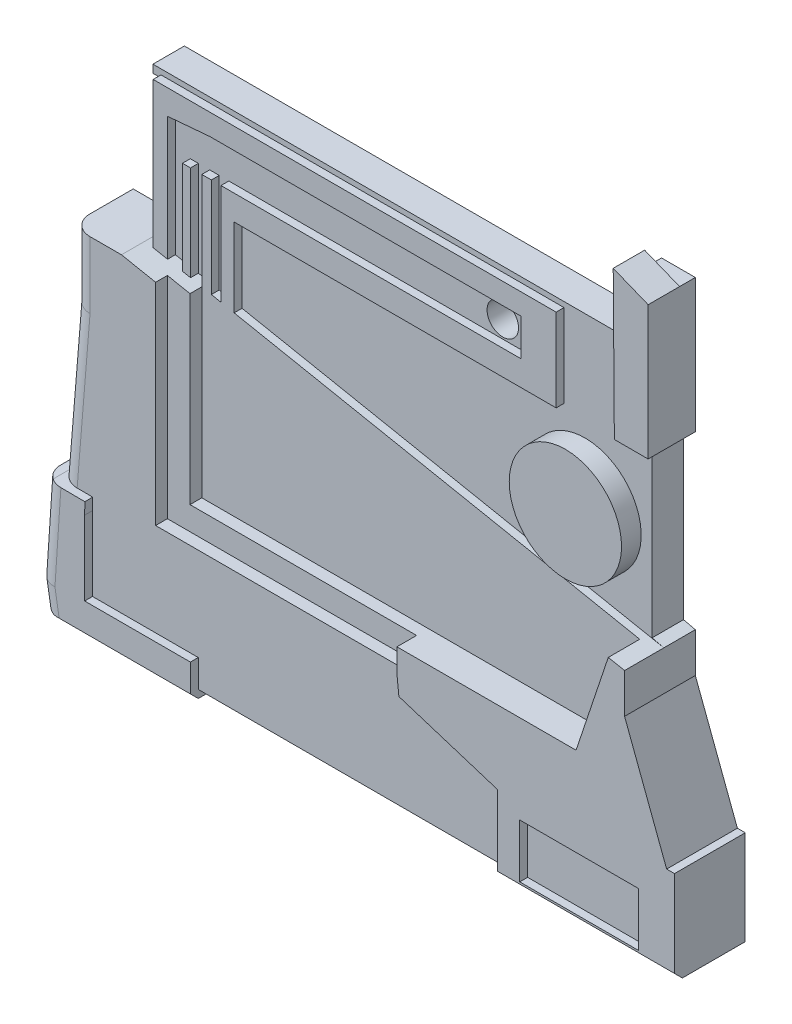
SolidWorks part; units mm, degrees
ref_plane "Front Plane" through (0, 0, 0) normal (0, 0, 1) x (1, 0, 0)
ref_plane "Top Plane" through (0, 0, 0) normal (0, 1, 0) x (1, 0, 0)
ref_plane "Right Plane" through (0, 0, 0) normal (1, 0, 0) x (0, 0, -1)
sketch "Sketch1" plane through (0, 0, 0) normal (0, 0, 1) x (1, 0, 0)
  line L0 (-79.7915, -39) -> (-81.3264, -61.8874)
  line L1 (-81.3264, -61.8874) -> (-79.9736, -70)
  line L2 (-79.9736, -70) -> (81.3264, -70)
  line L3 (81.3264, -70) -> (81.3264, -46)
  line L4 (81.3264, -46) -> (79.3264, -46)
  line L5 (79.3264, -46) -> (68.6264, -17.7)
  line L6 (68.6264, -17.7) -> (68.6264, -7.6)
  line L7 (68.6264, -7.6) -> (65.6264, -6.9)
  line L8 (65.6264, -6.9) -> (65.6264, 36)
  line L9 (65.6264, 36) -> (68.6264, 36)
  line L10 (68.6264, 36) -> (68.6264, 70)
  line L11 (68.6264, 70) -> (60.0264, 70)
  line L12 (60.0264, 70) -> (60.0264, 56)
  line L13 (60.0264, 56) -> (-61.3736, 56)
  line L14 (-61.3736, 56) -> (-61.3736, 53.9822)
  line L15 (-61.3736, 53.9822) -> (-59.3736, 54)
  line L16 (-59.3736, 54) -> (-59.3736, 50)
  line L17 (-59.3736, 50) -> (-61.3736, 50)
  line L18 (-61.3736, 50) -> (-61.3736, 34)
  line L19 (-61.3736, 34) -> (-59.3736, 34)
  line L20 (-59.3736, 34) -> (-59.3736, 30)
  line L21 (-59.3736, 30) -> (-61.3736, 30)
  line L22 (-61.3736, 30) -> (-61.3736, 18)
  line L23 (-61.3736, 18) -> (-74.3888, 18)
  line L24 (-74.3888, 18) -> (-74.3735, 1.2008)
  line L25 (-74.3735, 1.2008) -> (-77.6658, -39)
  line L26 (-77.6658, -39) -> (-79.7915, -39)
extrude "Boss-Extrude1" add sketch "Sketch1" along normal blind 8
sketch "Sketch2" plane through (0, 0, 8) normal (0, 0, 1) x (1, 0, 0)
  line L0 (-74.3888, 18) -> (-61.3736, 18)
  line L1 (-61.3736, 18) -> (68.6264, -7.6)
  line L2 (68.6264, -7.6) -> (68.6264, -17.7)
  line L3 (68.6264, -17.7) -> (79.3264, -46)
  line L4 (79.3264, -46) -> (81.3264, -46)
  line L5 (81.3264, -46) -> (81.3264, -70)
  line L6 (81.3264, -70) -> (-79.9736, -70)
  line L7 (-79.9736, -70) -> (-81.3264, -61.8874)
  line L8 (-81.3264, -61.8874) -> (-79.7915, -39)
  line L9 (-79.7915, -39) -> (-77.6658, -39)
  line L10 (-77.6658, -39) -> (-74.3735, 1.2008)
  line L11 (-74.3735, 1.2008) -> (-74.3888, 18)
extrude "Boss-Extrude2" add sketch "Sketch2" along normal blind 10
sketch "Sketch3" plane through (0, 0, 8) normal (0, 0, 1) x (1, 0, 0)
  circle A0 centre (48.5663, 14.327) radius 14.2858
extrude "Boss-Extrude3" add sketch "Sketch3" along normal blind 5
sketch "Sketch4" plane through (0, 0, 8) normal (0, 0, 1) x (1, 0, 0)
  line L0 (59.7365, 73.5779) -> (68.6264, 70)
  line L1 (68.6264, 70) -> (68.6264, 36)
  line L2 (68.6264, 36) -> (60.0264, 36)
  line L3 (60.0264, 36) -> (59.7365, 73.5779)
extrude "Boss-Extrude4" add sketch "Sketch4" along normal blind 4 and the other way blind 4
sketch "Sketch5" plane through (0, 0, 18) normal (0, 0, 1) x (1, 0, 0)
  line L0 (-46.9367, 15.1571) -> (-46.9367, -31.333)
  line L1 (68.6264, -7.6) -> (-61.3736, 18) construction
  line L2 (-46.9367, -31.333) -> (56.2824, -31.333)
  line L3 (56.2824, -31.333) -> (64.4799, -6.7835)
  line L4 (68.6264, -7.6) -> (-61.3736, 18) construction
  line L5 (64.4799, -6.7835) -> (-46.9367, 15.1571)
extrude "Cut-Extrude1" cut sketch "Sketch5" against normal blind 8
sketch "Sketch6" plane through (0, 0, 18) normal (0, 0, 1) x (1, 0, 0)
  line L0 (-46.9367, 15.1571) -> (-52.6867, 16.2894)
  line L1 (-46.9367, 15.1571) -> (-61.3736, 18) construction
  line L2 (-52.6867, 16.2894) -> (-52.6867, -37.3099)
  line L6 (-46.9367, 15.1571) -> (-46.9367, -31.333)
  line L11 (-52.6867, -37.3099) -> (10.7086, -37.3099)
  line L12 (10.7086, -37.3099) -> (10.7086, -31.333)
  line L13 (-46.9367, -31.333) -> (56.2824, -31.333) construction
  line L14 (10.7086, -31.333) -> (-46.9367, -31.333)
extrude "Cut-Extrude3" cut sketch "Sketch6" against normal blind 5
sketch "Sketch7" plane through (0, 0, 18) normal (0, 0, 1) x (1, 0, 0)
  line L0 (-52.6867, 16.2894) -> (-57.0301, 17.1447)
  line L1 (-52.6867, 16.2894) -> (-61.3736, 18) construction
  line L2 (-57.0301, 17.1447) -> (-57.0301, -42.0416)
  line L3 (-57.0301, -42.0416) -> (11.2067, -42.0416)
  line L4 (11.2067, -42.0416) -> (10.7086, -37.3099)
  line L5 (10.7086, -37.3099) -> (-52.6867, -37.3099)
  line L6 (-52.6867, -37.3099) -> (-52.6867, 16.2894)
extrude "Cut-Extrude4" cut sketch "Sketch7" against normal blind 2
sketch "Sketch8" plane through (0, 0, 18) normal (0, 0, 1) x (1, 0, 0)
  line L0 (-68.7343, -42.0416) -> (-68.7343, -60.9684)
  line L1 (-68.7343, -60.9684) -> (-41.8383, -60.9684)
  line L2 (-41.8383, -60.9684) -> (-41.8383, -70)
  line L3 (-79.9736, -70) -> (81.3264, -70) construction
  line L4 (-41.8383, -70) -> (36.3594, -70)
  line L5 (36.3594, -70) -> (36.3594, -50.0108)
  line L6 (36.3594, -50.0108) -> (11.2067, -42.0416)
  line L7 (11.2067, -42.0416) -> (-68.7343, -42.0416)
extrude "Cut-Extrude7" cut sketch "Sketch8" against normal blind 2
sketch "Sketch9" plane through (0, 0, 18) normal (0, 0, 1) x (1, 0, 0)
  line L0 (-57.0301, -42.0416) -> (-57.0301, 17.1447)
  line L1 (-57.0301, 17.1447) -> (-61.3736, 18)
  line L2 (-61.3736, 18) -> (-67.8812, 18)
  line L3 (-61.3736, 18) -> (-74.3888, 18) construction
  line L4 (-67.8812, 18) -> (-68.7343, -42.0416)
  line L5 (-68.7343, -42.0416) -> (-57.0301, -42.0416)
extrude "Cut-Extrude8" cut sketch "Sketch9" against normal blind 2
sketch "Sketch10" plane through (0, 0, 18) normal (0, 0, 1) x (1, 0, 0)
  line L0 (-74.3888, 18) -> (-67.8812, 18)
  line L1 (-67.8812, 18) -> (-68.6918, -39.0538)
  line L2 (-67.8812, 18) -> (-68.7343, -42.0416) construction
  line L3 (-68.6918, -39.0538) -> (-77.6658, -39)
  line L4 (-77.6658, -39) -> (-74.3735, 1.2008)
  line L5 (-74.3735, 1.2008) -> (-74.3888, 18)
extrude "Cut-Extrude9" cut sketch "Sketch10" against normal blind 2
sketch "Sketch11" plane through (0, 0, 18) normal (0, 0, 1) x (1, 0, 0)
  line L1 (41.9541, -53.861) -> (72.2151, -53.861)
  line L2 (41.9541, -53.861) -> (41.9541, -67.5033)
  line L3 (41.9541, -67.5033) -> (72.2151, -67.5033)
  line L4 (72.2151, -53.861) -> (72.2151, -67.5033)
  line L5 (41.9541, -53.861) -> (72.2151, -67.5033) construction
  line L6 (41.9541, -67.5033) -> (72.2151, -53.861) construction
  point P4 (57.0846, -60.6821)
extrude "Cut-Extrude10" cut sketch "Sketch11" against normal blind 2
sketch "Sketch12" plane through (0, 0, 8) normal (0, 0, 1) x (1, 0, 0)
  circle A0 centre (27.6431, 44.3743) radius 4
extrude "Cut-Extrude11" cut sketch "Sketch12" against normal blind 61
sketch "Sketch13" plane through (0, 0, 8) normal (0, 0, 1) x (1, 0, 0)
  line L0 (-38.7062, 13.5363) -> (-38.7062, 33.559)
  line L1 (68.6264, -7.6) -> (-61.3736, 18) construction
  line L2 (-38.7062, 33.559) -> (43.2167, 33.559)
  line L3 (43.2167, 33.559) -> (43.2167, 54.6643)
  line L4 (43.2167, 54.6643) -> (-44.8401, 54.6643)
  line L5 (-44.8401, 54.6643) -> (-44.8401, 49.3004)
  line L6 (-44.8401, 49.3004) -> (34.2804, 49.3004)
  line L7 (34.2804, 49.3004) -> (34.2804, 39.9136)
  line L8 (34.2804, 39.9136) -> (-42.0615, 39.9136)
  line L9 (-42.0615, 39.9136) -> (-42.0615, 14.197)
  line L10 (64.4799, -6.7835) -> (-46.9367, 15.1571) construction
  line L11 (-42.0615, 14.197) -> (-38.7062, 13.5363)
extrude "Boss-Extrude5" add sketch "Sketch13" along normal blind 2
sketch "Sketch14" plane through (0, 0, 8) normal (0, 0, 1) x (1, 0, 0)
  line L0 (-44.8401, 54.6643) -> (-59.3134, 54.6643)
  line L1 (-59.3134, 54.6643) -> (-59.3134, 17.5943)
  line L2 (-52.6867, 16.2894) -> (-61.3736, 18) construction
  line L3 (-59.3134, 17.5943) -> (-55.6524, 16.8734)
  line L4 (-42.0615, 14.197) -> (-61.3736, 18) construction
  line L5 (-55.6524, 16.8734) -> (-55.6524, 48.3725)
  line L6 (-55.6524, 48.3725) -> (-44.8401, 49.3004)
  line L7 (-44.8401, 54.6643) -> (-44.8401, 49.3004)
extrude "Boss-Extrude6" add sketch "Sketch14" along normal blind 2
sketch "Sketch15" plane through (0, 0, 8) normal (0, 0, 1) x (1, 0, 0)
  line L0 (-55.6524, 16.8734) -> (-52.6867, 16.2894)
  line L1 (-44.4991, 14.677) -> (-44.4991, 39.923)
  line L2 (-42.0615, 14.197) -> (-46.9367, 15.1571) construction
  line L3 (-44.4991, 14.677) -> (-46.9367, 15.1571)
  line L4 (-46.9367, 15.1571) -> (-46.9367, 39.923)
  line L5 (-46.9367, 39.923) -> (-44.4991, 39.923)
  line L6 (-49.8117, 15.7232) -> (-51.8625, 16.1271)
  line L7 (-46.9367, 15.1571) -> (-52.6867, 16.2894) construction
  line L8 (-42.0615, 14.197) -> (-55.6524, 16.8734) construction
  line L9 (-51.8625, 16.1271) -> (-51.8625, 39.923)
  line L10 (-51.8625, 39.923) -> (-49.8117, 39.923)
  line L11 (-49.8117, 39.923) -> (-49.8117, 15.7232)
extrude "Boss-Extrude7" add sketch "Sketch15" along normal blind 2 contours L11 L10 L9 L6 | L4 L5 L1 L3
chamfer "Chamfer3" distance 2 angle 45 3 edges at (58.8429, -70, 18) (-60.9059, -70, 18) (-2.7394, -70, 16)
fillet "Fillet3" radius 5 5 edges at (-80.1403, -69, 17) (-80.8168, -64.9437, 18) (-80.5589, -50.4437, 18) (-74.3812, 9.6004, 16) (-76.0196, -18.8996, 16)
